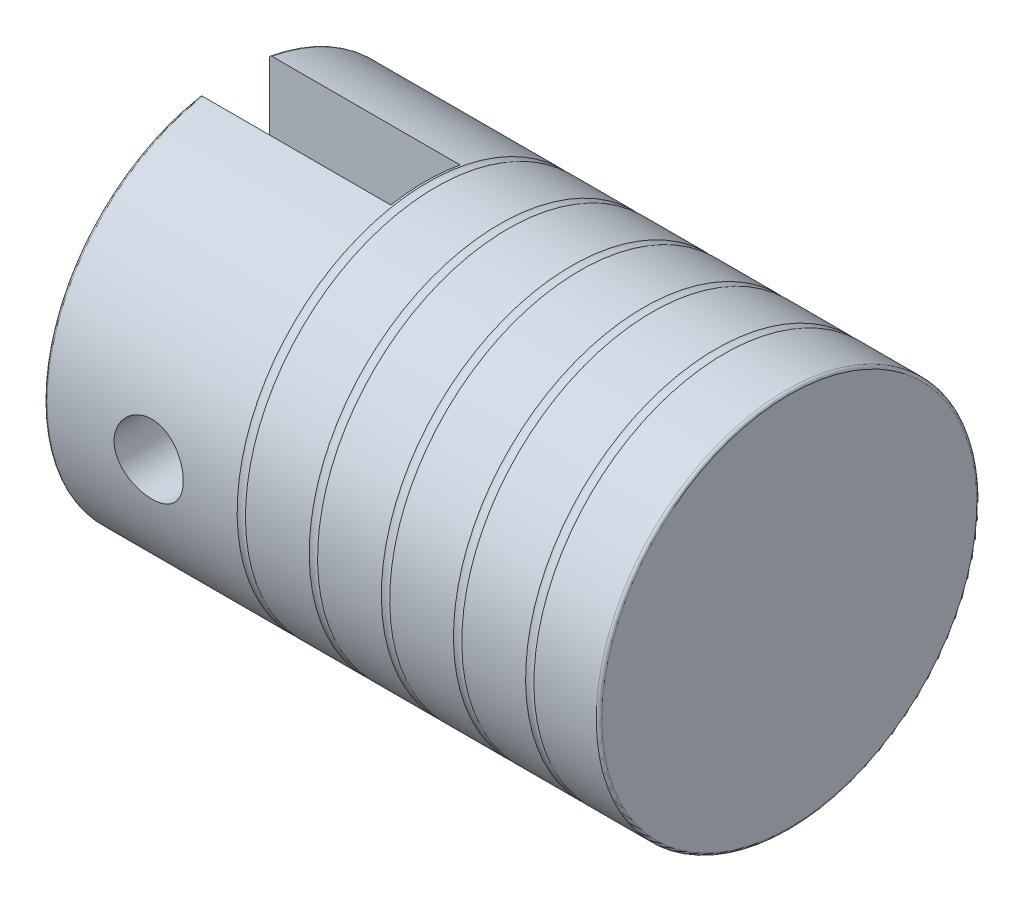
SolidWorks part; units mm, degrees
material "6061-T6 (SS)"
ref_plane "Front Plane" through (0, 0, 0) normal (0, 0, 1) x (1, 0, 0)
ref_plane "Top Plane" through (0, 0, 0) normal (0, 1, 0) x (1, 0, 0)
ref_plane "Right Plane" through (0, 0, 0) normal (1, 0, 0) x (0, 0, -1)
sketch "Sketch1" plane through (0, 0, 0) normal (0, 0, 1) x (1, 0, 0)
  line L0 (22.4155, 8.7122) -> (25.4, 8.7122)
  line L1 (0, 0) -> (25.4, 0)
  line L2 (0, 0) -> (0, 8.7122)
  line L3 (0, 8.7122) -> (8.8265, 8.7122)
  line L4 (25.4, 0) -> (25.4, 8.7122)
  line L5 (19.1135, 8.7122) -> (22.0345, 8.7122)
  line L6 (15.8115, 8.7122) -> (18.7325, 8.7122)
  line L7 (12.5095, 8.7122) -> (15.4305, 8.7122)
  line L8 (9.2075, 8.7122) -> (12.1285, 8.7122)
  arc A0 (22.0345, 8.7122) -> (22.4155, 8.7122) centre (22.225, 9.0422) ccw
  arc A1 (18.7325, 8.7122) -> (19.1135, 8.7122) centre (18.923, 9.0422) ccw
  arc A2 (15.4305, 8.7122) -> (15.8115, 8.7122) centre (15.621, 9.0422) ccw
  arc A3 (12.1285, 8.7122) -> (12.5095, 8.7122) centre (12.319, 9.0422) ccw
  arc A4 (8.8265, 8.7122) -> (9.2075, 8.7122) centre (9.017, 9.0422) ccw
  dimension "D4" = 60
  dimension "D3" = 0.381
  dimension "D1" = 25.4
  dimension "D2" = 8.7122
  dimension "D5" = 3.175
  dimension "D7" = 2.921
  dimension "D6" = 5
revolve "Revolve1" add sketch "Sketch1" angle 360 about L1
sketch "Sketch2" plane through (0, 0, 0) normal (0, 0, 1) x (1, 0, 0)
  line L0 (4.7752, 0) -> (0, 0) construction
  circle A0 centre (4.7752, 0) radius 1.6002
  dimension "D2" = 3.2004
  dimension "D1" = 4.7752
extrude "Cut-Extrude1" cut sketch "Sketch2" against normal through all and the other way blind 5.08
ref_plane "Plane2" through (0, 0, 8.7122) normal (0, 0, 1) x (1, 0, 0)
sketch "Sketch3" plane through (0, 0, 8.7122) normal (0, 0, 1) x (1, 0, 0)
  line L0 (0, 0) -> (4.7752, 0) construction
  line L1 (0, 8.7122) -> (0, -8.7122) construction
  circle A0 centre (4.7752, 0) radius 1.5837
  dimension "D2" = 3.1674
  dimension "D1" = 4.7752
extrude "Cut-Extrude2" cut sketch "Sketch3" against normal up to next
sketch "Sketch4" plane through (0, 0, 0) normal (1, 0, 0) x (0, 0, -1)
  line L1 (1.5875, -12.7) -> (-1.5875, -12.7)
  line L2 (1.5875, -12.7) -> (1.5875, 12.7)
  line L3 (1.5875, 12.7) -> (-1.5875, 12.7)
  line L4 (-1.5875, -12.7) -> (-1.5875, 12.7)
  line L5 (1.5875, -12.7) -> (-1.5875, 12.7) construction
  line L6 (1.5875, 12.7) -> (-1.5875, -12.7) construction
  point P0 (0, 0)
  dimension "D1" = 25.4
  dimension "D2" = 3.175
extrude "Cut-Extrude3" cut sketch "Sketch4" along normal blind 8.7376
fillet "Fillet1" radius 0.127 3 edges at (25.4, -8.7122, 0) (0, 0, -8.7122) (0, 0, 8.7122)
